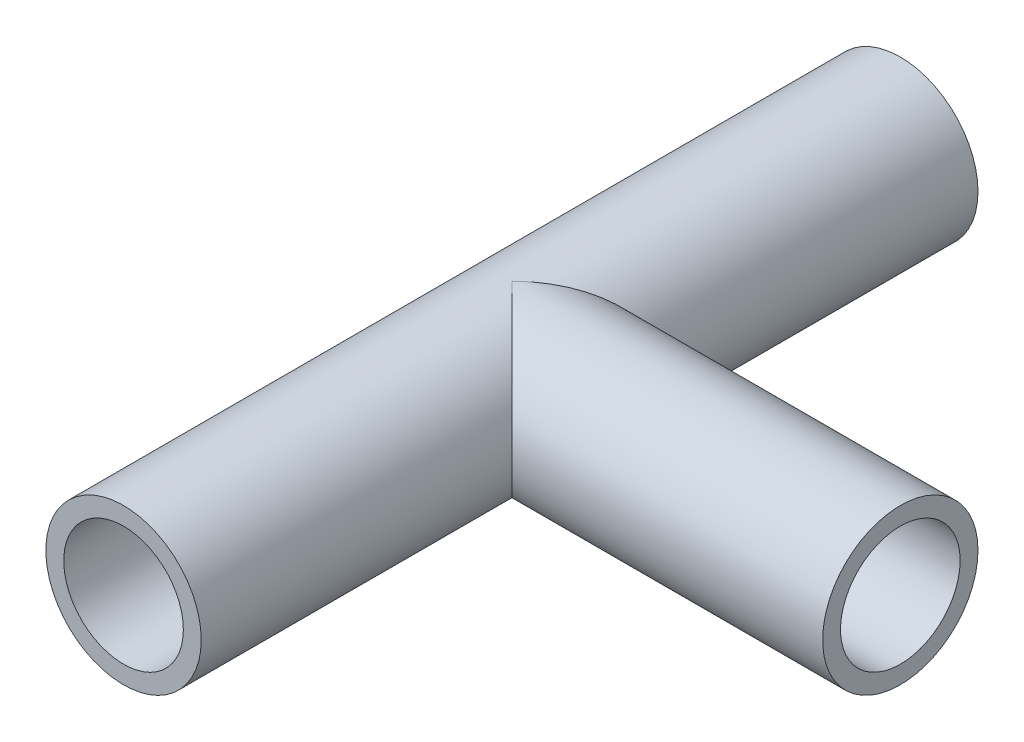
SolidWorks part; units mm, degrees
ref_plane "Front Plane" through (0, 0, 0) normal (0, 0, 1) x (1, 0, 0)
ref_plane "Top Plane" through (0, 0, 0) normal (0, 1, 0) x (1, 0, 0)
ref_plane "Right Plane" through (0, 0, 0) normal (1, 0, 0) x (0, 0, -1)
sketch "Sketch12" plane through (0, 0, 0) normal (0, 0, 1) x (1, 0, 0)
  circle A0 centre (0, 0) radius 10
  dimension "D1" = 20
extrude "Boss-Extrude2" add sketch "Sketch12" along normal blind 100
sketch "Sketch13" plane through (0, 0, 0) normal (1, 0, 0) x (0, 0, -1)
  line L0 (-100, 0) -> (0, 0) construction
  line L1 (-100, 10) -> (-100, -10) construction
  circle A0 centre (-50, 0) radius 10
extrude "Boss-Extrude3" add sketch "Sketch13" along normal blind 50
shell "Shell7" thickness 2.3 removed face at (50, 0, 40) removed face at (10, 0, 0) removed face at (10, 0, 100)
